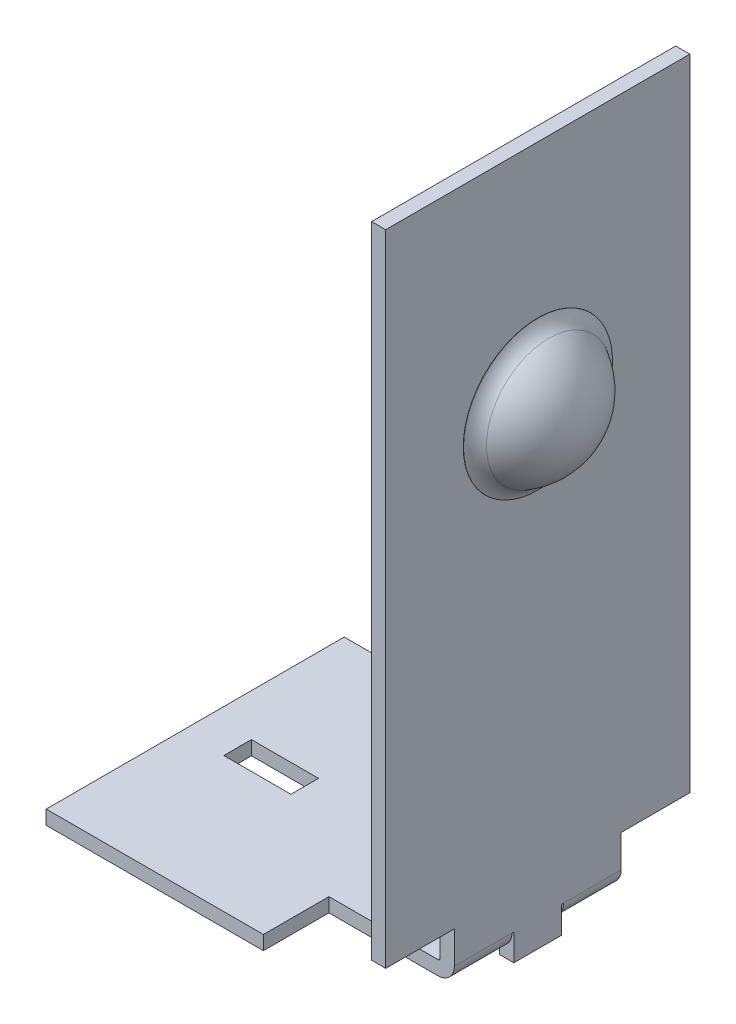
SolidWorks part; units mm, degrees
material "Saf Altın"
ref_plane "Ön Düzlem" through (0, 0, 0) normal (0, 0, 1) x (1, 0, 0)
ref_plane "Üst Düzlem" through (0, 0, 0) normal (0, 1, 0) x (1, 0, 0)
ref_plane "Sağ Düzlem" through (0, 0, 0) normal (1, 0, 0) x (0, 0, -1)
sketch "Çizim1" plane through (0, 0, 0) normal (0, 0, 1) x (1, 0, 0)
  line L0 (-0.3, 0.35) -> (-0.3, 13.55) construction
  line L1 (-0.3, 0.35) -> (-0.3, 14.676)
  line L2 (-36.2839, 13.5501) -> (-36.2839, 0.3548) construction
  line L3 (0, 0.35) -> (0, 13.55) construction
  line L8 (-0.35, 0.3) -> (-7.3, 0.3)
  line L9 (-0.35, 0) -> (-7.3, 0)
  line L10 (0, 0.35) -> (0, 14.676)
  line L13 (-7.3, 0.3) -> (-7.3, 0)
  line L15 (-0.3, 14.676) -> (0, 14.676)
  line L21 (-36.2839, 0.0035) -> (-36.2839, -0.2248) construction
  line L22 (-36.2839, -0.2248) -> (-35.9791, -0.2195) construction
  line L23 (-35.9791, -0.2195) -> (-35.9791, 0.3548) construction
  line L24 (-43.2308, 0) -> (-38.6025, 0) construction
  line L25 (-38.6025, 0) -> (-38.6025, 0.3048) construction
  line L26 (-38.6025, 0.3048) -> (-43.2308, 0.3048) construction
  line L27 (-43.2308, 0.3048) -> (-43.2308, 0) construction
  line L28 (-36.2839, 1.0419) -> (-36.2839, 0.3548) construction
  line L29 (-36.3339, 0.3048) -> (-38.6025, 0.3048) construction
  line L30 (-38.6025, 0.3048) -> (-38.6025, 0) construction
  line L31 (-38.6025, 0) -> (-36.3339, 0) construction
  line L32 (-35.9791, 0.3548) -> (-35.9791, 1.0419) construction
  line L33 (-35.9791, 1.0419) -> (-36.2839, 1.0419) construction
  line L34 (-35.9791, 1.0419) -> (-35.9791, 13.5501) construction
  line L35 (-34.4379, 13.9448) -> (-32.3807, 10.1913) construction
  line L36 (-32.3088, 9.9105) -> (-32.3088, 7.112) construction
  line L37 (-32.3088, 7.112) -> (-32.004, 7.112) construction
  line L38 (-32.004, 7.112) -> (-32.004, 9.9105) construction
  line L39 (-32.1134, 10.3378) -> (-34.1706, 14.0913) construction
  line L40 (-36.2839, 13.5501) -> (-36.2839, 1.0419) construction
  line L41 (-36.2839, 1.0419) -> (-35.9791, 1.0419) construction
  line L42 (1.8134, 14.0912) -> (3.8707, 10.3381) construction
  line L43 (3.9803, 9.9103) -> (3.9803, 7.1103) construction
  line L44 (1.5503, 13.947) -> (3.6076, 10.1939) construction
  line L45 (3.6803, 9.9103) -> (3.6803, 7.1103) construction
  arc A2 (-0.3, 0.35) -> (-0.35, 0.3) centre (-0.35, 0.35) cw
  arc A3 (0, 0.35) -> (-0.35, 0) centre (-0.35, 0.35) cw
  arc A7 (-36.2839, 0.0035) -> (-35.9791, 0.3548) centre (-36.3339, 0.3548) ccw construction
  arc A8 (-36.3339, 0.3048) -> (-36.2839, 0.3548) centre (-36.3339, 0.3548) ccw construction
  arc A9 (-36.3339, 0) -> (-35.9791, 0.3548) centre (-36.3339, 0.3548) ccw construction
  arc A10 (-34.4379, 13.9448) -> (-35.9791, 13.5501) centre (-35.158, 13.5501) ccw construction
  arc A11 (-32.3088, 9.9105) -> (-32.3807, 10.1913) centre (-32.893, 9.9105) ccw construction
  arc A12 (-32.004, 9.9105) -> (-32.1134, 10.3378) centre (-32.893, 9.9105) ccw construction
  arc A13 (-34.1706, 14.0913) -> (-36.2839, 13.5501) centre (-35.158, 13.5501) ccw construction
  arc A14 (3.6076, 10.1939) -> (3.6803, 9.9103) centre (3.0903, 9.9103) cw construction
  arc A15 (3.8707, 10.3381) -> (3.9803, 9.9103) centre (3.0903, 9.9103) cw construction
  arc A16 (0, 13.55) -> (1.5503, 13.947) centre (0.826, 13.55) cw construction
  arc A17 (-0.3, 13.55) -> (1.8134, 14.0912) centre (0.826, 13.55) cw construction
  dimension "D5" = 1.1259
  dimension "D8" = 0.889
  dimension "D15" = 0.05
  dimension "D1" = 13.5501
  dimension "D2" = 14.676
  dimension "D3" = 13.1953
  dimension "D4" = 13.1953
  dimension "D9" = 4.2802
  dimension "D12" = 2.7985
  dimension "D14" = 6.9469
  dimension "D16" = 6.95
  dimension "D17" = 0.3
extrude "Yükseklik-Ekstrüzyon1" add sketch "Çizim1" along normal mid plane 6.48
sketch "Çizim2" plane through (0, 0, 0) normal (0, 1, 0) x (1, 0, 0)
  line L1 (-7.3, -3.24) -> (-7.3, 3.24) construction
  line L3 (0, -4) -> (0, -1.778)
  line L4 (0, 4) -> (-8, 4)
  line L5 (-8, 4) -> (-8, -4)
  line L6 (-8, -4) -> (0, -4)
  line L7 (0, 1.778) -> (0, 4)
  line L13 (-2.6717, 1.778) -> (-2.6717, 3.175)
  line L14 (0, 1.778) -> (-2.6717, 1.778)
  line L15 (-2.6717, 3.175) -> (-7.3, 3.175)
  line L16 (-7.3, 3.175) -> (-7.3, -3.175)
  line L17 (-7.3, -3.175) -> (-2.6717, -3.175)
  line L18 (-2.6717, -3.175) -> (-2.6717, -1.778)
  line L19 (-2.6717, -1.778) -> (0, -1.778)
  line L20 (-4.966, -0.2942) -> (-4.966, 0.2942)
  line L21 (-4.966, 0.2942) -> (-6.396, 0.2942)
  line L22 (-6.396, 0.2942) -> (-6.396, -0.2942)
  line L23 (-6.396, -0.2942) -> (-4.966, -0.2942)
  point P18 (-4.966, 0)
  dimension "D1" = 0.5883
  dimension "D2" = 1.43
  dimension "D3" = 4.6283
  dimension "D5" = 1.397
  dimension "D6" = 1.397
  dimension "D7" = 6.35
  dimension "D8" = 0.904
  dimension "D9" = 2.8808
  dimension "D4" = 4
  dimension "D10" = 8
  dimension "D11" = 8
extrude "Kes-Ekstrüzyon1" cut sketch "Çizim2" along normal blind 1.0419
sketch "Çizim4" plane through (0, 0, 0) normal (1, 0, 0) x (0, 0, -1)
  line L0 (-1.778, 0.35) -> (1.778, 0.35) construction
  line L1 (-0.55, -0.15) -> (0.55, -0.15)
  line L2 (-0.55, -0.15) -> (-0.55, 0.33)
  line L3 (-0.53, 0.35) -> (0.53, 0.35)
  line L4 (0.55, -0.15) -> (0.55, 0.33)
  arc A0 (0.53, 0.35) -> (0.55, 0.33) centre (0.53, 0.33) cw
  arc A1 (-0.55, 0.33) -> (-0.53, 0.35) centre (-0.53, 0.33) cw
  dimension "D4" = 0.02
  dimension "D1" = 1.1
  dimension "D2" = 0.55
  dimension "D3" = 0.5
extrude "Kes-Ekstrüzyon2" cut sketch "Çizim4" against normal blind 0.5
sketch "Çizim5" plane through (0, 0, 0) normal (1, 0, 0) x (0, 0, -1)
  line L0 (0.53, 0.35) -> (-0.53, 0.35) construction
  line L1 (-0.51, -0.22) -> (0.51, -0.22)
  line L2 (-0.51, -0.22) -> (-0.51, 0.33)
  line L3 (-0.53, 0.35) -> (0.53, 0.35)
  line L4 (0.51, -0.22) -> (0.51, 0.33)
  line L5 (-0.51, -0.22) -> (0.51, 0.35) construction
  line L6 (-0.51, 0.35) -> (0.51, -0.22) construction
  line L7 (-1.778, 0.35) -> (-0.53, 0.35) construction
  arc A0 (-0.53, 0.35) -> (-0.51, 0.33) centre (-0.53, 0.33) cw
  arc A1 (0.53, 0.35) -> (0.51, 0.33) centre (0.53, 0.33) ccw
  point P0 (0, 0.065)
  dimension "D1" = 1.02
  dimension "D2" = 0.57
  dimension "D3" = 0.02
extrude "Yükseklik-Ekstrüzyon2" add sketch "Çizim5" against normal blind 0.3
sketch "Çizim6" plane through (0, 0, 0) normal (0, 0, 1) x (1, 0, 0)
  line L0 (-0.3, 8.2677) -> (3, 8.2677) construction
  line L1 (3, 8.2677) -> (3, 11.4283) construction
  line L2 (3, 11.4283) -> (-2.9904, 11.4283) construction
  line L3 (0.716, 9.8408) -> (1.0208, 9.8408)
  line L4 (-0.3, 14.676) -> (-0.3, 1.0419) construction
  line L5 (-0.3, 11.4283) -> (0.0048, 11.4283)
  line L11 (0.0048, 8.2677) -> (0.0048, 11.4283) construction
  line L13 (-0.3, 11.4283) -> (-0.3, 8.2677) construction
  arc A13 (-0.3, 11.4283) -> (-0.2789, 11.3169) centre (0.0048, 11.4283) ccw
  arc A14 (-0.2789, 11.3169) -> (0.0875, 10.9009) centre (0.4776, 11.614) ccw
  arc A15 (0.0048, 11.4283) -> (0.2338, 11.1683) centre (0.4776, 11.614) ccw
  arc A16 (1.0208, 9.8408) -> (0.2338, 11.1683) centre (-0.4924, 9.8408) ccw
  arc A17 (0.716, 9.8408) -> (0.0875, 10.9009) centre (-0.4924, 9.8408) ccw
  dimension "D3" = 1.2084
  dimension "D1" = 0.8128
  dimension "D2" = 0.508
  dimension "D4" = 0.3048
  dimension "D5" = 1.5132
  dimension "D6" = 1.5875
  dimension "D7" = 0.1924
  dimension "D8" = 3.1606
  dimension "D9" = 9.8408
  dimension "D10" = 3
sketch "Çizim7" plane through (0, 0, 0) normal (1, 0, 0) x (0, 0, -1)
  line L0 (0, 11.4283) -> (0, 8.2677) construction
  line L1 (0, 11.4283) -> (0, 8.2677) construction
  circle A0 centre (0, 9.848) radius 1.5803
extrude "Kes-Ekstrüzyon3" cut sketch "Çizim7" against normal blind 0.3
ref_axis "Eksen1" through (-0.4924, 9.8408, 0) along (1, 0, 0)
revolve "Döndür1" add sketch "Çizim6" angle 360 about axis through (-0.4924, 9.8408, 0) along (1, 0, 0)
equation "\"D10@Çizim2\"=2*\"D4@Çizim2\""
equation "\"D2@Çizim4\"=\"D1@Çizim4\"/2"
